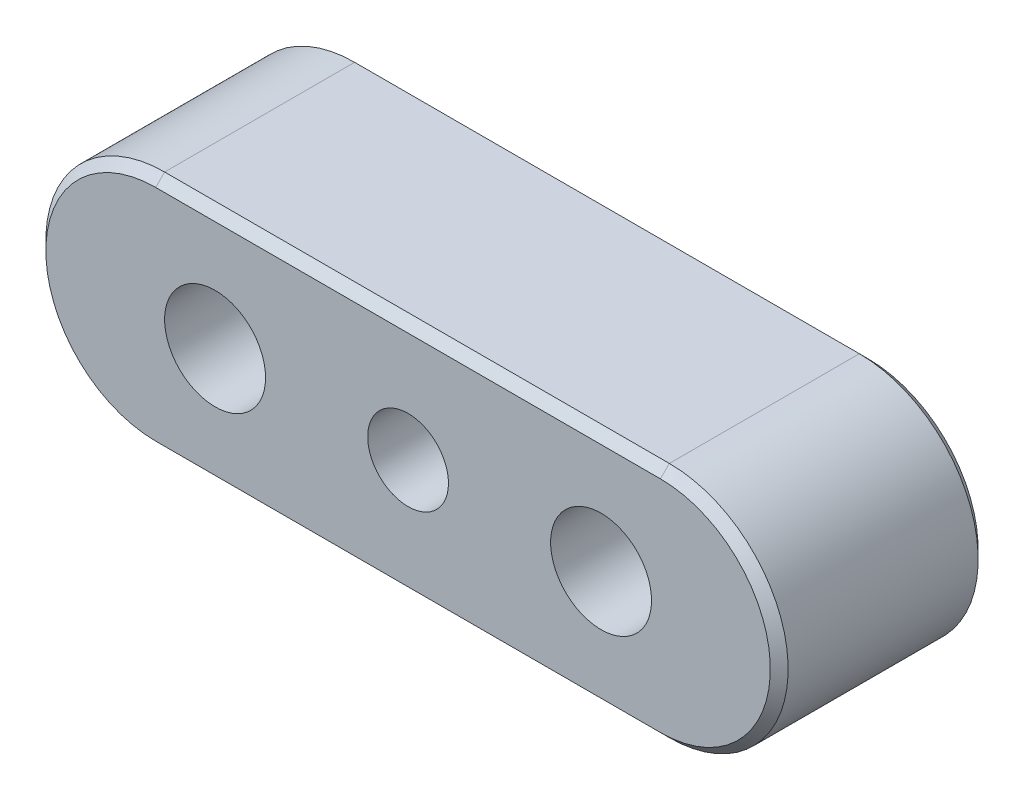
SolidWorks part; units mm, degrees
ref_plane "Front" through (0, 0, 0) normal (0, 0, 1) x (1, 0, 0)
ref_plane "Top" through (0, 0, 0) normal (0, 1, 0) x (1, 0, 0)
ref_plane "Right" through (0, 0, 0) normal (1, 0, 0) x (0, 0, -1)
sketch "Sketch1" plane through (0, 0, 0) normal (0, 0, 1) x (1, 0, 0)
  line L0 (-17, 4) -> (0, 4)
  line L1 (0, -4) -> (-17, -4)
  arc A0 (0, 4) -> (0, -4) centre (0, 0) cw
  arc A1 (-17, -4) -> (-17, 4) centre (-17, 0) cw
  dimension "b" = 8
  dimension "L" = 25
extrude "BaseKey" add sketch "Sketch1" along normal mid plane 7
sketch "Sketch2" plane through (0, 0, 0) normal (0, 0, 1) x (1, 0, 0)
  circle A0 centre (-8.5, 0) radius 1.36
  arc A1 (-17, 4) -> (-17, -4) centre (-17, 0) ccw construction
  circle A2 centre (-2, 0) radius 1.7
  circle A3 centre (-15, 0) radius 1.7
  arc A4 (-17, 4) -> (-17, -4) centre (-17, 0) ccw construction
  point P2 (-21, 0)
  point P12 (-21, 0)
  dimension "L3" = 6
  dimension "L2" = 12.5
extrude "Hole" cut sketch "Sketch2" against normal through all and the other way through all
cosmetic thread "ThreadCosmetic1" [suppressed] parameters "dp"=2.992
chamfer "EndChamfer" distance 0.3 angle 60 1 edges at (-7.14, 0, -3.5) first distance on face at (-7.14, 0, -3.5)
sketch "Sketch3" plane through (-2.246, 3.1335, -3.5) normal (0, 0, -1) x (-1, 0, 0)
  circle A0 centre (-0.246, -3.1335) radius 3
  circle A1 centre (12.754, -3.1335) radius 3
  dimension "D" = 6
extrude "Hole1" cut sketch "Sketch3" against normal blind 2.4
sketch "Sketch4" plane through (9.2132, 0.6398, 3.5) normal (0, 0, 1) x (1, 0, 0)
  line L0 (-9.2132, 3.3602) -> (-5.2132, 3.3602)
  line L1 (-30.2132, 3.3602) -> (-26.2132, 3.3602)
  line L2 (-30.2132, 3.3602) -> (-30.2132, -0.6398)
  line L3 (-5.2132, 3.3602) -> (-5.2132, -0.6398)
  line L4 (-9.2132, 3.3602) -> (-26.2132, 3.3602) construction
  arc A0 (-9.2132, -4.6398) -> (-9.2132, 3.3602) centre (-9.2132, -0.6398) ccw construction
  arc A1 (-26.2132, 3.3602) -> (-30.2132, -0.6398) centre (-26.2132, -0.6398) ccw
  arc A2 (-26.2132, 3.3602) -> (-26.2132, -4.6398) centre (-26.2132, -0.6398) ccw construction
  arc A3 (-5.2132, -0.6398) -> (-9.2132, 3.3602) centre (-9.2132, -0.6398) ccw
extrude "Extrude1" [suppressed] add sketch "Sketch4" against normal up to surface (7 mm away) up to face at (-18, 0, -3.5)
sketch "Sketch5" plane through (0.5609, 3.4098, 3.5) normal (0, 0, 1) x (1, 0, 0)
  line L0 (-21.5609, -3.4098) -> (-21.5609, -7.4098)
  line L1 (-21.5609, -7.4098) -> (-17.5609, -7.4098)
  line L2 (-0.5609, -7.4098) -> (3.4391, -7.4098)
  line L3 (3.4391, -3.4098) -> (3.4391, -7.4098)
  line L5 (-17.5609, -7.4098) -> (-0.5609, -7.4098) construction
  arc A0 (-0.5609, -7.4098) -> (-0.5609, 0.5902) centre (-0.5609, -3.4098) ccw construction
  arc A1 (-21.5609, -3.4098) -> (-17.5609, -7.4098) centre (-17.5609, -3.4098) ccw
  arc A2 (-17.5609, 0.5902) -> (-17.5609, -7.4098) centre (-17.5609, -3.4098) ccw construction
  arc A3 (-0.5609, -7.4098) -> (3.4391, -3.4098) centre (-0.5609, -3.4098) ccw
extrude "Extrude2" [suppressed] add sketch "Sketch5" against normal up to surface (7 mm away) up to face at (-18, 0, -3.5)
chamfer "Chamfer1" distance 0.3 angle 45 8 edges at (4, 0, -3.5) (-8.5, 4, -3.5) (-21, 0, -3.5) (-8.5, -4, -3.5) (4, 0, 3.5) (-8.5, -4, 3.5) (-21, 0, 3.5) (-8.5, 4, 3.5)
sketch "Sketch6" plane through (0, 0, 0) normal (0, 1, 0) x (1, 0, 0)
  line L0 (-8.5, -5.1617) -> (-8.5, 5.7636) construction
  line L1 (-9.86, -3.5) -> (-7.14, -3.5) construction
  line L2 (-9.86, -3.5) -> (-7.14, -3.5) construction
  line L3 (-9.9778, -3.5) -> (-9.86, -3.568)
  line L4 (-9.86, -3.568) -> (-9.724, -3.568)
  line L5 (-9.724, -3.568) -> (-9.724, -3.432)
  line L6 (-9.724, -3.432) -> (-9.86, -3.432)
  line L7 (-9.86, -3.432) -> (-9.9778, -3.5)
  dimension "D1" = 0.136
  dimension "D2" = 2.72
revolve "Cut-Revolve10" [suppressed] cut sketch "Sketch6" angle 360 about L0
pattern_linear "LPattern10" [suppressed] count 41 spacing 0.1632 along (0, 0, -1) of bodies 106
equation "\"d@Sketch2\" = \"d0@Sketch2\" * 0.8"
equation "\"D2@Sketch6\" = \"d@Sketch2\""
equation "\"D1@Sketch6\" =  (0.1 *  \"d@Sketch2\" )  / 2"
equation "\"D3@LPattern10\" = \"D1@Sketch6\" * 1.2"
equation "\"D1@LPattern10\" =  ( \"h@BaseKey\" - \"c1@EndChamfer\" )  / \"D3@LPattern10\""
equation "\"dp@ThreadCosmetic1\" = \"d@Sketch2\" * 1.1"
